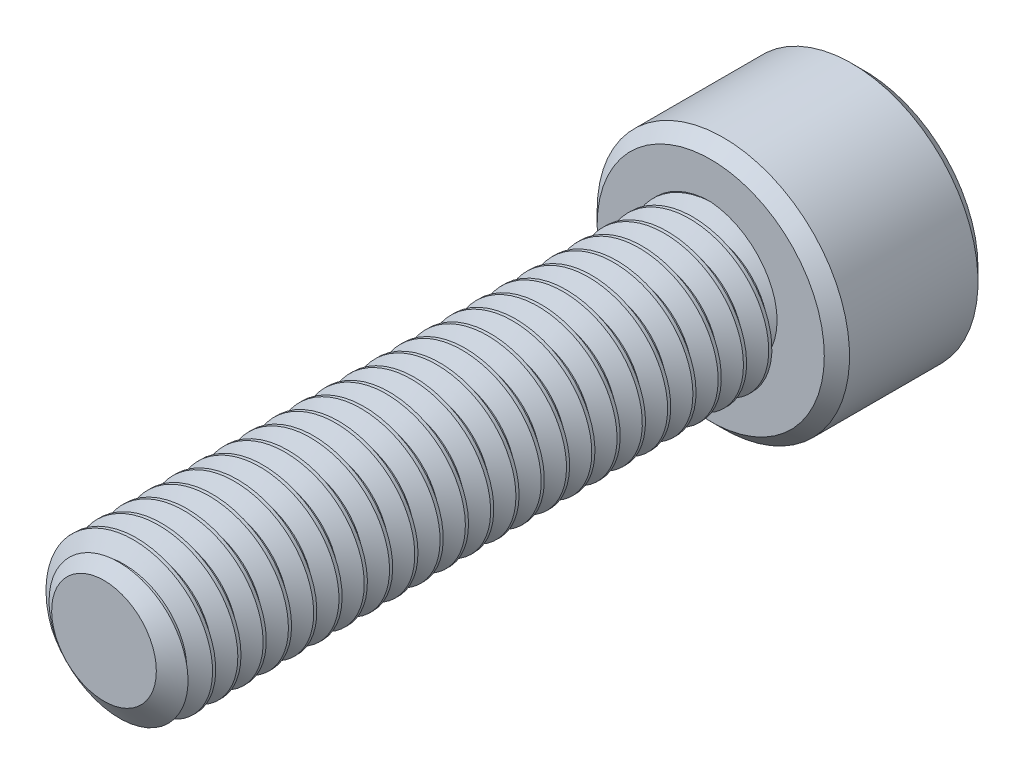
SolidWorks part; units mm, degrees
other "DetailItem1"
ref_plane "Front Plane" through (0, 0, 0) normal (0, 0, 1) x (1, 0, 0)
ref_plane "Top Plane" through (0, 0, 0) normal (0, 1, 0) x (1, 0, 0)
ref_plane "Right Plane" through (0, 0, 0) normal (1, 0, 0) x (0, 0, -1)
sketch "Sketch1" plane through (0, 0, 0) normal (0, 0, 1) x (1, 0, 0)
  circle A0 centre (0, 0) radius 2.413
  dimension "OD" = 4.826
extrude "Extrude1" add sketch "Sketch1" against normal blind 19.05
sketch "Sketch2" plane through (0, 0, 0) normal (0, 0, 1) x (1, 0, 0)
  circle A0 centre (0, 0) radius 2.413 construction
  circle A1 centre (0, 0) radius 2.413
curve "Helix/Spiral1" pitch 0.7937 height 19.8438 turns 25 parameters "pitch"=0.7937
sketch "Sketch3" plane through (0, 0, 0) normal (1, 0, 0) x (0, 0, -1)
  line L0 (-0.6945, 2.413) -> (-0.3969, 1.8974)
  line L1 (-0.3969, 1.8974) -> (-0.2977, 1.8974)
  line L2 (-0.2977, 1.8974) -> (0, 2.413)
  line L3 (-0.6945, 2.413) -> (0, 2.413)
  line L4 (-0.3473, 2.413) -> (-0.3473, 1.8974) construction
  line L5 (-0.5457, 2.1552) -> (-0.1488, 2.1552) construction
  line L6 (0, 2.413) -> (0, -2.413) construction
  dimension "D1" = 0.0992
  dimension "D2" = 0.3969
  dimension "D3" = 60
sweep "Cut-Sweep1" cut profiles "Sketch3" path "Helix/Spiral1"
sketch "Sketch4" plane through (0, 0, 0) normal (1, 0, 0) x (0, 0, -1)
  line L0 (0.5388, 2.413) -> (0, 1.6434)
  line L1 (0, 1.6434) -> (0, 2.413)
  line L2 (0.5388, 2.413) -> (0, 2.413)
  line L3 (-0.6945, 2.413) -> (0, 2.413) construction
  line L4 (0, 0) -> (7.0209, 0) construction
  dimension "D1" = 55
  dimension "D2" = 0.254
revolve "Cut-Revolve1" cut sketch "Sketch4" angle 360 about L4
sketch "Sketch6" plane through (0, 0, -19.05) normal (0, 0, -1) x (-1, 0, 0)
  circle A0 centre (0, 0) radius 3.9624
  dimension "head dia" = 7.9248
extrude "Extrude2" add sketch "Sketch6" along normal blind 4.826
sketch "Sketch7" plane through (0, 0, -23.876) normal (0, 0, -1) x (-1, 0, 0)
  line L1 (0, 2.2914) -> (-1.9844, 1.1457)
  line L2 (-1.9844, 1.1457) -> (-1.9844, -1.1457)
  line L3 (-1.9844, -1.1457) -> (0, -2.2914)
  line L4 (0, -2.2914) -> (1.9844, -1.1457)
  line L5 (1.9844, -1.1457) -> (1.9844, 1.1457)
  line L6 (1.9844, 1.1457) -> (0, 2.2914)
  circle A0 centre (0, 0) radius 1.9844 construction
  dimension "hex dia" = 3.9688
extrude "Cut-Extrude1" cut sketch "Sketch7" against normal blind 2.9766
sketch "Sketch8" plane through (0, 0, -23.876) normal (0, 0, -1) x (-1, 0, 0)
  circle A0 centre (0, 0) radius 2.2914
extrude "Cut-Extrude2" cut sketch "Sketch8" against normal through all draft 45
chamfer "Chamfer1" distance 0.3962 angle 45 2 edges at (-3.9624, 0, -23.876) (-3.9624, 0, -19.05)
sketch "Sketch10" plane through (0, 0, -19.05) normal (0, 0, 1) x (1, 0, 0)
  circle A1 centre (0, 0) radius 2.413
  circle A2 centre (0, 0) radius 2.413
  dimension "D1" = 0
ref_plane "Plane1" through (0, 0, -31.75) normal (0, 0, 1) x (1, 0, 0)
extrude "partial thread" [suppressed] add sketch "Sketch10" along normal up to surface (12.7 mm away) separate body
chamfer "Chamfer2" [suppressed] distance 0.0965 angle 45
combine bodies "Combine1" [suppressed] operation type add bodies to combine 107 108
sketch "Sketch9" plane through (0, 0, 0) normal (1, 0, 0) x (0, 0, -1)
  line L0 (0, 2.413) -> (0, -2.413) construction
  line L1 (1.9844, 2.413) -> (1.9844, -2.413) construction
  dimension "D1" = 1.9844
equation "\"D3@Helix/Spiral1\" = \"screw length@Extrude1\"+\"pitch@Helix/Spiral1\""
equation "\"D1@Sketch3\" = \"pitch@Helix/Spiral1\"*.125"
equation "\"D2@Sketch3\" = \"pitch@Helix/Spiral1\"*.5"
equation "\"D1@Cut-Extrude1\" = \"hex dia@Sketch7\"*.75"
equation "\"D1@Chamfer1\" = \"head dia@Sketch6\"*.05"
equation "\"D1@Sketch9\" = \"pitch@Helix/Spiral1\"*2.5"
equation "\"D1@Chamfer2\"=\"OD@Sketch1\"*.02"
